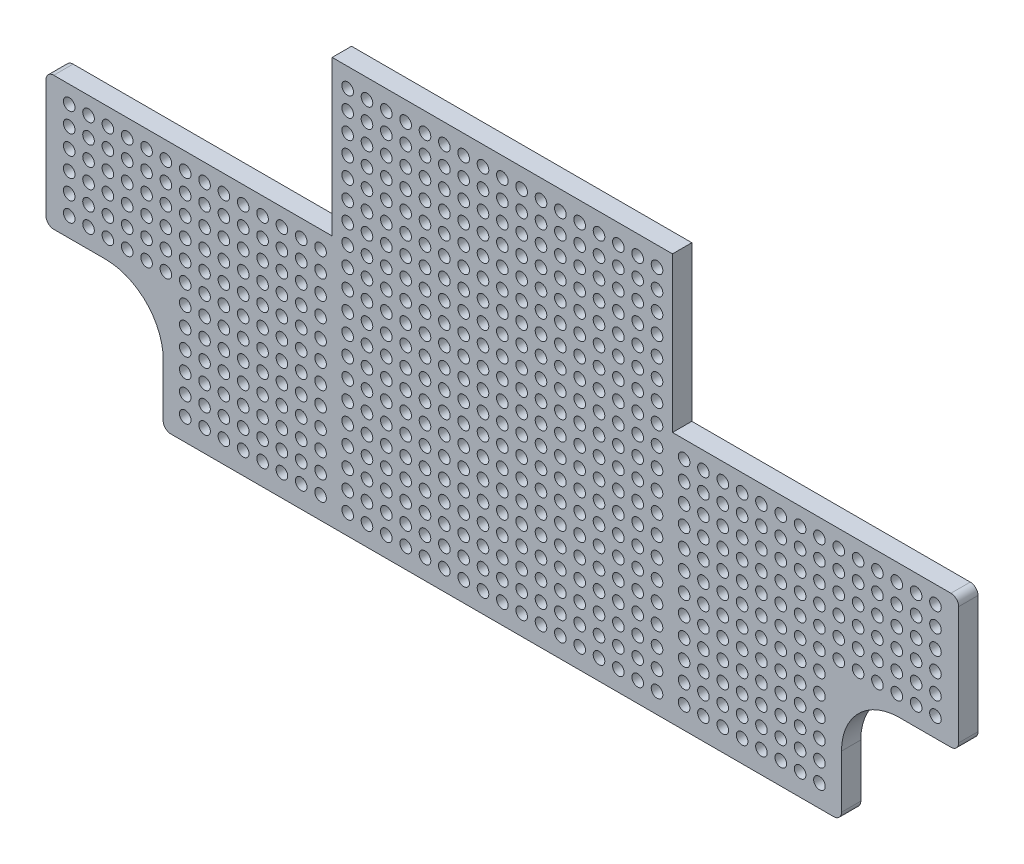
SolidWorks part; units mm, degrees
ref_plane "Plan de face" through (0, 0, 0) normal (0, 0, 1) x (1, 0, 0)
ref_plane "Plan de dessus" through (0, 0, 0) normal (0, 1, 0) x (1, 0, 0)
ref_plane "Plan de droite" through (0, 0, 0) normal (1, 0, 0) x (0, 0, -1)
sketch "Esquisse1" plane through (0, 0, 0) normal (0, 0, 1) x (1, 0, 0)
  line L0 (0, 0) -> (236, 0)
  line L1 (236, 0) -> (236, 65.2)
  line L2 (236, 65.2) -> (162, 65.2)
  line L3 (162, 65.2) -> (162, 105.2)
  line L4 (162, 105.2) -> (74, 105.2)
  line L5 (74, 105.2) -> (74, 65.2)
  line L6 (74, 65.2) -> (0, 65.2)
  line L7 (0, 65.2) -> (0, 0)
  line L8 (0, 30.7) -> (33, 30.7)
  line L10 (236, 30.7) -> (203, 30.7)
  line L12 (30.3, 30.7) -> (30.3, 0)
  line L13 (205.7, 30.7) -> (205.7, 0)
  circle A0 centre (15.3, 15.7) radius 15
  circle A1 centre (220.7, 15.7) radius 15
  circle A2 centre (78, 85.2) radius 1.5
  circle A3 centre (98, 85.2) radius 1.5
  circle A4 centre (118, 85.2) radius 1.5
  circle A5 centre (138, 85.2) radius 1.5
  circle A6 centre (158, 85.2) radius 1.5
  circle A7 centre (6, 55.7) radius 1.5
  circle A8 centre (26, 55.7) radius 1.5
  circle A9 centre (26, 35.7) radius 1.5
  circle A10 centre (6, 35.7) radius 1.5
  circle A11 centre (210, 55.7) radius 1.5
  circle A12 centre (230, 55.7) radius 1.5
  circle A13 centre (210, 35.7) radius 1.5
  circle A14 centre (230, 35.7) radius 1.5
  circle A15 centre (83, 85.2) radius 1.5
  circle A16 centre (88, 85.2) radius 1.5
  circle A17 centre (93, 85.2) radius 1.5
  circle A18 centre (98, 85.2) radius 1.5
  circle A19 centre (103, 85.2) radius 1.5
  circle A20 centre (108, 85.2) radius 1.5
  circle A21 centre (113, 85.2) radius 1.5
  circle A22 centre (118, 85.2) radius 1.5
  circle A23 centre (123, 85.2) radius 1.5
  circle A24 centre (128, 85.2) radius 1.5
  circle A25 centre (133, 85.2) radius 1.5
  circle A26 centre (138, 85.2) radius 1.5
  circle A27 centre (143, 85.2) radius 1.5
  circle A28 centre (148, 85.2) radius 1.5
  circle A29 centre (153, 85.2) radius 1.5
  circle A30 centre (158, 85.2) radius 1.5
  circle A31 centre (83, 90.2) radius 1.5
  circle A32 centre (88, 90.2) radius 1.5
  circle A33 centre (93, 90.2) radius 1.5
  circle A34 centre (98, 90.2) radius 1.5
  circle A35 centre (103, 90.2) radius 1.5
  circle A36 centre (108, 90.2) radius 1.5
  circle A37 centre (113, 90.2) radius 1.5
  circle A38 centre (118, 90.2) radius 1.5
  circle A39 centre (123, 90.2) radius 1.5
  circle A40 centre (128, 90.2) radius 1.5
  circle A41 centre (133, 90.2) radius 1.5
  circle A42 centre (138, 90.2) radius 1.5
  circle A43 centre (143, 90.2) radius 1.5
  circle A44 centre (148, 90.2) radius 1.5
  circle A45 centre (153, 90.2) radius 1.5
  circle A46 centre (158, 90.2) radius 1.5
  circle A47 centre (83, 95.2) radius 1.5
  circle A48 centre (88, 95.2) radius 1.5
  circle A49 centre (93, 95.2) radius 1.5
  circle A50 centre (98, 95.2) radius 1.5
  circle A51 centre (103, 95.2) radius 1.5
  circle A52 centre (108, 95.2) radius 1.5
  circle A53 centre (113, 95.2) radius 1.5
  circle A54 centre (118, 95.2) radius 1.5
  circle A55 centre (123, 95.2) radius 1.5
  circle A56 centre (128, 95.2) radius 1.5
  circle A57 centre (133, 95.2) radius 1.5
  circle A58 centre (138, 95.2) radius 1.5
  circle A59 centre (143, 95.2) radius 1.5
  circle A60 centre (148, 95.2) radius 1.5
  circle A61 centre (153, 95.2) radius 1.5
  circle A62 centre (158, 95.2) radius 1.5
  circle A63 centre (83, 100.2) radius 1.5
  circle A64 centre (88, 100.2) radius 1.5
  circle A65 centre (93, 100.2) radius 1.5
  circle A66 centre (98, 100.2) radius 1.5
  circle A67 centre (103, 100.2) radius 1.5
  circle A68 centre (108, 100.2) radius 1.5
  circle A69 centre (113, 100.2) radius 1.5
  circle A70 centre (118, 100.2) radius 1.5
  circle A71 centre (123, 100.2) radius 1.5
  circle A72 centre (128, 100.2) radius 1.5
  circle A73 centre (133, 100.2) radius 1.5
  circle A74 centre (138, 100.2) radius 1.5
  circle A75 centre (143, 100.2) radius 1.5
  circle A76 centre (148, 100.2) radius 1.5
  circle A77 centre (153, 100.2) radius 1.5
  circle A78 centre (158, 100.2) radius 1.5
  circle A79 centre (78, 90.2) radius 1.5
  circle A80 centre (78, 95.2) radius 1.5
  circle A81 centre (78, 100.2) radius 1.5
  circle A82 centre (83, 85.2) radius 1.5
  circle A83 centre (88, 85.2) radius 1.5
  circle A84 centre (93, 85.2) radius 1.5
  circle A85 centre (98, 85.2) radius 1.5
  circle A86 centre (103, 85.2) radius 1.5
  circle A87 centre (108, 85.2) radius 1.5
  circle A88 centre (113, 85.2) radius 1.5
  circle A89 centre (118, 85.2) radius 1.5
  circle A90 centre (123, 85.2) radius 1.5
  circle A91 centre (128, 85.2) radius 1.5
  circle A92 centre (133, 85.2) radius 1.5
  circle A93 centre (138, 85.2) radius 1.5
  circle A94 centre (143, 85.2) radius 1.5
  circle A95 centre (148, 85.2) radius 1.5
  circle A96 centre (153, 85.2) radius 1.5
  circle A97 centre (158, 85.2) radius 1.5
  circle A98 centre (83, 80.2) radius 1.5
  circle A99 centre (88, 80.2) radius 1.5
  circle A100 centre (93, 80.2) radius 1.5
  circle A101 centre (98, 80.2) radius 1.5
  circle A102 centre (103, 80.2) radius 1.5
  circle A103 centre (108, 80.2) radius 1.5
  circle A104 centre (113, 80.2) radius 1.5
  circle A105 centre (118, 80.2) radius 1.5
  circle A106 centre (123, 80.2) radius 1.5
  circle A107 centre (128, 80.2) radius 1.5
  circle A108 centre (133, 80.2) radius 1.5
  circle A109 centre (138, 80.2) radius 1.5
  circle A110 centre (143, 80.2) radius 1.5
  circle A111 centre (148, 80.2) radius 1.5
  circle A112 centre (153, 80.2) radius 1.5
  circle A113 centre (158, 80.2) radius 1.5
  circle A114 centre (83, 75.2) radius 1.5
  circle A115 centre (88, 75.2) radius 1.5
  circle A116 centre (93, 75.2) radius 1.5
  circle A117 centre (98, 75.2) radius 1.5
  circle A118 centre (103, 75.2) radius 1.5
  circle A119 centre (108, 75.2) radius 1.5
  circle A120 centre (113, 75.2) radius 1.5
  circle A121 centre (118, 75.2) radius 1.5
  circle A122 centre (123, 75.2) radius 1.5
  circle A123 centre (128, 75.2) radius 1.5
  circle A124 centre (133, 75.2) radius 1.5
  circle A125 centre (138, 75.2) radius 1.5
  circle A126 centre (143, 75.2) radius 1.5
  circle A127 centre (148, 75.2) radius 1.5
  circle A128 centre (153, 75.2) radius 1.5
  circle A129 centre (158, 75.2) radius 1.5
  circle A130 centre (83, 70.2) radius 1.5
  circle A131 centre (88, 70.2) radius 1.5
  circle A132 centre (93, 70.2) radius 1.5
  circle A133 centre (98, 70.2) radius 1.5
  circle A134 centre (103, 70.2) radius 1.5
  circle A135 centre (108, 70.2) radius 1.5
  circle A136 centre (113, 70.2) radius 1.5
  circle A137 centre (118, 70.2) radius 1.5
  circle A138 centre (123, 70.2) radius 1.5
  circle A139 centre (128, 70.2) radius 1.5
  circle A140 centre (133, 70.2) radius 1.5
  circle A141 centre (138, 70.2) radius 1.5
  circle A142 centre (143, 70.2) radius 1.5
  circle A143 centre (148, 70.2) radius 1.5
  circle A144 centre (153, 70.2) radius 1.5
  circle A145 centre (158, 70.2) radius 1.5
  circle A146 centre (83, 65.2) radius 1.5
  circle A147 centre (88, 65.2) radius 1.5
  circle A148 centre (93, 65.2) radius 1.5
  circle A149 centre (98, 65.2) radius 1.5
  circle A150 centre (103, 65.2) radius 1.5
  circle A151 centre (108, 65.2) radius 1.5
  circle A152 centre (113, 65.2) radius 1.5
  circle A153 centre (118, 65.2) radius 1.5
  circle A154 centre (123, 65.2) radius 1.5
  circle A155 centre (128, 65.2) radius 1.5
  circle A156 centre (133, 65.2) radius 1.5
  circle A157 centre (138, 65.2) radius 1.5
  circle A158 centre (143, 65.2) radius 1.5
  circle A159 centre (148, 65.2) radius 1.5
  circle A160 centre (153, 65.2) radius 1.5
  circle A161 centre (158, 65.2) radius 1.5
  circle A162 centre (78, 80.2) radius 1.5
  circle A163 centre (78, 75.2) radius 1.5
  circle A164 centre (78, 70.2) radius 1.5
  circle A165 centre (78, 65.2) radius 1.5
  circle A166 centre (11, 55.7) radius 1.5
  circle A167 centre (16, 55.7) radius 1.5
  circle A168 centre (21, 55.7) radius 1.5
  circle A169 centre (26, 55.7) radius 1.5
  circle A170 centre (31, 55.7) radius 1.5
  circle A171 centre (36, 55.7) radius 1.5
  circle A172 centre (41, 55.7) radius 1.5
  circle A173 centre (46, 55.7) radius 1.5
  circle A174 centre (51, 55.7) radius 1.5
  circle A175 centre (56, 55.7) radius 1.5
  circle A176 centre (61, 55.7) radius 1.5
  circle A177 centre (66, 55.7) radius 1.5
  circle A178 centre (71, 55.7) radius 1.5
  circle A179 centre (11, 60.7) radius 1.5
  circle A180 centre (16, 60.7) radius 1.5
  circle A181 centre (21, 60.7) radius 1.5
  circle A182 centre (26, 60.7) radius 1.5
  circle A183 centre (31, 60.7) radius 1.5
  circle A184 centre (36, 60.7) radius 1.5
  circle A185 centre (41, 60.7) radius 1.5
  circle A186 centre (46, 60.7) radius 1.5
  circle A187 centre (51, 60.7) radius 1.5
  circle A188 centre (56, 60.7) radius 1.5
  circle A189 centre (61, 60.7) radius 1.5
  circle A190 centre (66, 60.7) radius 1.5
  circle A191 centre (71, 60.7) radius 1.5
  circle A192 centre (6, 60.7) radius 1.5
  circle A193 centre (11, 55.7) radius 1.5
  circle A194 centre (16, 55.7) radius 1.5
  circle A195 centre (21, 55.7) radius 1.5
  circle A196 centre (26, 55.7) radius 1.5
  circle A197 centre (31, 55.7) radius 1.5
  circle A198 centre (36, 55.7) radius 1.5
  circle A199 centre (41, 55.7) radius 1.5
  circle A200 centre (46, 55.7) radius 1.5
  circle A201 centre (51, 55.7) radius 1.5
  circle A202 centre (56, 55.7) radius 1.5
  circle A203 centre (61, 55.7) radius 1.5
  circle A204 centre (66, 55.7) radius 1.5
  circle A205 centre (71, 55.7) radius 1.5
  circle A206 centre (11, 50.7) radius 1.5
  circle A207 centre (16, 50.7) radius 1.5
  circle A208 centre (21, 50.7) radius 1.5
  circle A209 centre (26, 50.7) radius 1.5
  circle A210 centre (31, 50.7) radius 1.5
  circle A211 centre (36, 50.7) radius 1.5
  circle A212 centre (41, 50.7) radius 1.5
  circle A213 centre (46, 50.7) radius 1.5
  circle A214 centre (51, 50.7) radius 1.5
  circle A215 centre (56, 50.7) radius 1.5
  circle A216 centre (61, 50.7) radius 1.5
  circle A217 centre (66, 50.7) radius 1.5
  circle A218 centre (71, 50.7) radius 1.5
  circle A219 centre (11, 45.7) radius 1.5
  circle A220 centre (16, 45.7) radius 1.5
  circle A221 centre (21, 45.7) radius 1.5
  circle A222 centre (26, 45.7) radius 1.5
  circle A223 centre (31, 45.7) radius 1.5
  circle A224 centre (36, 45.7) radius 1.5
  circle A225 centre (41, 45.7) radius 1.5
  circle A226 centre (46, 45.7) radius 1.5
  circle A227 centre (51, 45.7) radius 1.5
  circle A228 centre (56, 45.7) radius 1.5
  circle A229 centre (61, 45.7) radius 1.5
  circle A230 centre (66, 45.7) radius 1.5
  circle A231 centre (71, 45.7) radius 1.5
  circle A232 centre (11, 40.7) radius 1.5
  circle A233 centre (16, 40.7) radius 1.5
  circle A234 centre (21, 40.7) radius 1.5
  circle A235 centre (26, 40.7) radius 1.5
  circle A236 centre (31, 40.7) radius 1.5
  circle A237 centre (36, 40.7) radius 1.5
  circle A238 centre (41, 40.7) radius 1.5
  circle A239 centre (46, 40.7) radius 1.5
  circle A240 centre (51, 40.7) radius 1.5
  circle A241 centre (56, 40.7) radius 1.5
  circle A242 centre (61, 40.7) radius 1.5
  circle A243 centre (66, 40.7) radius 1.5
  circle A244 centre (71, 40.7) radius 1.5
  circle A245 centre (11, 35.7) radius 1.5
  circle A246 centre (16, 35.7) radius 1.5
  circle A247 centre (21, 35.7) radius 1.5
  circle A248 centre (26, 35.7) radius 1.5
  circle A249 centre (31, 35.7) radius 1.5
  circle A250 centre (36, 35.7) radius 1.5
  circle A251 centre (41, 35.7) radius 1.5
  circle A252 centre (46, 35.7) radius 1.5
  circle A253 centre (51, 35.7) radius 1.5
  circle A254 centre (56, 35.7) radius 1.5
  circle A255 centre (61, 35.7) radius 1.5
  circle A256 centre (66, 35.7) radius 1.5
  circle A257 centre (71, 35.7) radius 1.5
  circle A258 centre (6, 50.7) radius 1.5
  circle A259 centre (6, 45.7) radius 1.5
  circle A260 centre (6, 40.7) radius 1.5
  circle A261 centre (6, 35.7) radius 1.5
  circle A262 centre (41, 35.7) radius 1.5
  circle A263 centre (46, 35.7) radius 1.5
  circle A264 centre (51, 35.7) radius 1.5
  circle A265 centre (56, 35.7) radius 1.5
  circle A266 centre (61, 35.7) radius 1.5
  circle A267 centre (66, 35.7) radius 1.5
  circle A268 centre (71, 35.7) radius 1.5
  circle A269 centre (41, 30.7) radius 1.5
  circle A270 centre (46, 30.7) radius 1.5
  circle A271 centre (51, 30.7) radius 1.5
  circle A272 centre (56, 30.7) radius 1.5
  circle A273 centre (61, 30.7) radius 1.5
  circle A274 centre (66, 30.7) radius 1.5
  circle A275 centre (71, 30.7) radius 1.5
  circle A276 centre (41, 25.7) radius 1.5
  circle A277 centre (46, 25.7) radius 1.5
  circle A278 centre (51, 25.7) radius 1.5
  circle A279 centre (56, 25.7) radius 1.5
  circle A280 centre (61, 25.7) radius 1.5
  circle A281 centre (66, 25.7) radius 1.5
  circle A282 centre (71, 25.7) radius 1.5
  circle A283 centre (41, 20.7) radius 1.5
  circle A284 centre (46, 20.7) radius 1.5
  circle A285 centre (51, 20.7) radius 1.5
  circle A286 centre (56, 20.7) radius 1.5
  circle A287 centre (61, 20.7) radius 1.5
  circle A288 centre (66, 20.7) radius 1.5
  circle A289 centre (71, 20.7) radius 1.5
  circle A290 centre (41, 15.7) radius 1.5
  circle A291 centre (46, 15.7) radius 1.5
  circle A292 centre (51, 15.7) radius 1.5
  circle A293 centre (56, 15.7) radius 1.5
  circle A294 centre (61, 15.7) radius 1.5
  circle A295 centre (66, 15.7) radius 1.5
  circle A296 centre (71, 15.7) radius 1.5
  circle A297 centre (41, 10.7) radius 1.5
  circle A298 centre (46, 10.7) radius 1.5
  circle A299 centre (51, 10.7) radius 1.5
  circle A300 centre (56, 10.7) radius 1.5
  circle A301 centre (61, 10.7) radius 1.5
  circle A302 centre (66, 10.7) radius 1.5
  circle A303 centre (71, 10.7) radius 1.5
  circle A304 centre (41, 5.7) radius 1.5
  circle A305 centre (46, 5.7) radius 1.5
  circle A306 centre (51, 5.7) radius 1.5
  circle A307 centre (56, 5.7) radius 1.5
  circle A308 centre (61, 5.7) radius 1.5
  circle A309 centre (66, 5.7) radius 1.5
  circle A310 centre (71, 5.7) radius 1.5
  circle A311 centre (36, 30.7) radius 1.5
  circle A312 centre (36, 25.7) radius 1.5
  circle A313 centre (36, 20.7) radius 1.5
  circle A314 centre (36, 15.7) radius 1.5
  circle A315 centre (36, 10.7) radius 1.5
  circle A316 centre (36, 5.7) radius 1.5
  circle A317 centre (83, 65.2) radius 1.5
  circle A318 centre (88, 65.2) radius 1.5
  circle A319 centre (93, 65.2) radius 1.5
  circle A320 centre (98, 65.2) radius 1.5
  circle A321 centre (103, 65.2) radius 1.5
  circle A322 centre (108, 65.2) radius 1.5
  circle A323 centre (113, 65.2) radius 1.5
  circle A324 centre (118, 65.2) radius 1.5
  circle A325 centre (123, 65.2) radius 1.5
  circle A326 centre (128, 65.2) radius 1.5
  circle A327 centre (133, 65.2) radius 1.5
  circle A328 centre (138, 65.2) radius 1.5
  circle A329 centre (143, 65.2) radius 1.5
  circle A330 centre (148, 65.2) radius 1.5
  circle A331 centre (153, 65.2) radius 1.5
  circle A332 centre (158, 65.2) radius 1.5
  circle A333 centre (83, 60.2) radius 1.5
  circle A334 centre (88, 60.2) radius 1.5
  circle A335 centre (93, 60.2) radius 1.5
  circle A336 centre (98, 60.2) radius 1.5
  circle A337 centre (103, 60.2) radius 1.5
  circle A338 centre (108, 60.2) radius 1.5
  circle A339 centre (113, 60.2) radius 1.5
  circle A340 centre (118, 60.2) radius 1.5
  circle A341 centre (123, 60.2) radius 1.5
  circle A342 centre (128, 60.2) radius 1.5
  circle A343 centre (133, 60.2) radius 1.5
  circle A344 centre (138, 60.2) radius 1.5
  circle A345 centre (143, 60.2) radius 1.5
  circle A346 centre (148, 60.2) radius 1.5
  circle A347 centre (153, 60.2) radius 1.5
  circle A348 centre (158, 60.2) radius 1.5
  circle A349 centre (83, 55.2) radius 1.5
  circle A350 centre (88, 55.2) radius 1.5
  circle A351 centre (93, 55.2) radius 1.5
  circle A352 centre (98, 55.2) radius 1.5
  circle A353 centre (103, 55.2) radius 1.5
  circle A354 centre (108, 55.2) radius 1.5
  circle A355 centre (113, 55.2) radius 1.5
  circle A356 centre (118, 55.2) radius 1.5
  circle A357 centre (123, 55.2) radius 1.5
  circle A358 centre (128, 55.2) radius 1.5
  circle A359 centre (133, 55.2) radius 1.5
  circle A360 centre (138, 55.2) radius 1.5
  circle A361 centre (143, 55.2) radius 1.5
  circle A362 centre (148, 55.2) radius 1.5
  circle A363 centre (153, 55.2) radius 1.5
  circle A364 centre (158, 55.2) radius 1.5
  circle A365 centre (83, 50.2) radius 1.5
  circle A366 centre (88, 50.2) radius 1.5
  circle A367 centre (93, 50.2) radius 1.5
  circle A368 centre (98, 50.2) radius 1.5
  circle A369 centre (103, 50.2) radius 1.5
  circle A370 centre (108, 50.2) radius 1.5
  circle A371 centre (113, 50.2) radius 1.5
  circle A372 centre (118, 50.2) radius 1.5
  circle A373 centre (123, 50.2) radius 1.5
  circle A374 centre (128, 50.2) radius 1.5
  circle A375 centre (133, 50.2) radius 1.5
  circle A376 centre (138, 50.2) radius 1.5
  circle A377 centre (143, 50.2) radius 1.5
  circle A378 centre (148, 50.2) radius 1.5
  circle A379 centre (153, 50.2) radius 1.5
  circle A380 centre (158, 50.2) radius 1.5
  circle A381 centre (83, 45.2) radius 1.5
  circle A382 centre (88, 45.2) radius 1.5
  circle A383 centre (93, 45.2) radius 1.5
  circle A384 centre (98, 45.2) radius 1.5
  circle A385 centre (103, 45.2) radius 1.5
  circle A386 centre (108, 45.2) radius 1.5
  circle A387 centre (113, 45.2) radius 1.5
  circle A388 centre (118, 45.2) radius 1.5
  circle A389 centre (123, 45.2) radius 1.5
  circle A390 centre (128, 45.2) radius 1.5
  circle A391 centre (133, 45.2) radius 1.5
  circle A392 centre (138, 45.2) radius 1.5
  circle A393 centre (143, 45.2) radius 1.5
  circle A394 centre (148, 45.2) radius 1.5
  circle A395 centre (153, 45.2) radius 1.5
  circle A396 centre (158, 45.2) radius 1.5
  circle A397 centre (83, 40.2) radius 1.5
  circle A398 centre (88, 40.2) radius 1.5
  circle A399 centre (93, 40.2) radius 1.5
  circle A400 centre (98, 40.2) radius 1.5
  circle A401 centre (103, 40.2) radius 1.5
  circle A402 centre (108, 40.2) radius 1.5
  circle A403 centre (113, 40.2) radius 1.5
  circle A404 centre (118, 40.2) radius 1.5
  circle A405 centre (123, 40.2) radius 1.5
  circle A406 centre (128, 40.2) radius 1.5
  circle A407 centre (133, 40.2) radius 1.5
  circle A408 centre (138, 40.2) radius 1.5
  circle A409 centre (143, 40.2) radius 1.5
  circle A410 centre (148, 40.2) radius 1.5
  circle A411 centre (153, 40.2) radius 1.5
  circle A412 centre (158, 40.2) radius 1.5
  circle A413 centre (83, 35.2) radius 1.5
  circle A414 centre (88, 35.2) radius 1.5
  circle A415 centre (93, 35.2) radius 1.5
  circle A416 centre (98, 35.2) radius 1.5
  circle A417 centre (103, 35.2) radius 1.5
  circle A418 centre (108, 35.2) radius 1.5
  circle A419 centre (113, 35.2) radius 1.5
  circle A420 centre (118, 35.2) radius 1.5
  circle A421 centre (123, 35.2) radius 1.5
  circle A422 centre (128, 35.2) radius 1.5
  circle A423 centre (133, 35.2) radius 1.5
  circle A424 centre (138, 35.2) radius 1.5
  circle A425 centre (143, 35.2) radius 1.5
  circle A426 centre (148, 35.2) radius 1.5
  circle A427 centre (153, 35.2) radius 1.5
  circle A428 centre (158, 35.2) radius 1.5
  circle A429 centre (83, 30.2) radius 1.5
  circle A430 centre (88, 30.2) radius 1.5
  circle A431 centre (93, 30.2) radius 1.5
  circle A432 centre (98, 30.2) radius 1.5
  circle A433 centre (103, 30.2) radius 1.5
  circle A434 centre (108, 30.2) radius 1.5
  circle A435 centre (113, 30.2) radius 1.5
  circle A436 centre (118, 30.2) radius 1.5
  circle A437 centre (123, 30.2) radius 1.5
  circle A438 centre (128, 30.2) radius 1.5
  circle A439 centre (133, 30.2) radius 1.5
  circle A440 centre (138, 30.2) radius 1.5
  circle A441 centre (143, 30.2) radius 1.5
  circle A442 centre (148, 30.2) radius 1.5
  circle A443 centre (153, 30.2) radius 1.5
  circle A444 centre (158, 30.2) radius 1.5
  circle A445 centre (83, 25.2) radius 1.5
  circle A446 centre (88, 25.2) radius 1.5
  circle A447 centre (93, 25.2) radius 1.5
  circle A448 centre (98, 25.2) radius 1.5
  circle A449 centre (103, 25.2) radius 1.5
  circle A450 centre (108, 25.2) radius 1.5
  circle A451 centre (113, 25.2) radius 1.5
  circle A452 centre (118, 25.2) radius 1.5
  circle A453 centre (123, 25.2) radius 1.5
  circle A454 centre (128, 25.2) radius 1.5
  circle A455 centre (133, 25.2) radius 1.5
  circle A456 centre (138, 25.2) radius 1.5
  circle A457 centre (143, 25.2) radius 1.5
  circle A458 centre (148, 25.2) radius 1.5
  circle A459 centre (153, 25.2) radius 1.5
  circle A460 centre (158, 25.2) radius 1.5
  circle A461 centre (83, 20.2) radius 1.5
  circle A462 centre (88, 20.2) radius 1.5
  circle A463 centre (93, 20.2) radius 1.5
  circle A464 centre (98, 20.2) radius 1.5
  circle A465 centre (103, 20.2) radius 1.5
  circle A466 centre (108, 20.2) radius 1.5
  circle A467 centre (113, 20.2) radius 1.5
  circle A468 centre (118, 20.2) radius 1.5
  circle A469 centre (123, 20.2) radius 1.5
  circle A470 centre (128, 20.2) radius 1.5
  circle A471 centre (133, 20.2) radius 1.5
  circle A472 centre (138, 20.2) radius 1.5
  circle A473 centre (143, 20.2) radius 1.5
  circle A474 centre (148, 20.2) radius 1.5
  circle A475 centre (153, 20.2) radius 1.5
  circle A476 centre (158, 20.2) radius 1.5
  circle A477 centre (83, 15.2) radius 1.5
  circle A478 centre (88, 15.2) radius 1.5
  circle A479 centre (93, 15.2) radius 1.5
  circle A480 centre (98, 15.2) radius 1.5
  circle A481 centre (103, 15.2) radius 1.5
  circle A482 centre (108, 15.2) radius 1.5
  circle A483 centre (113, 15.2) radius 1.5
  circle A484 centre (118, 15.2) radius 1.5
  circle A485 centre (123, 15.2) radius 1.5
  circle A486 centre (128, 15.2) radius 1.5
  circle A487 centre (133, 15.2) radius 1.5
  circle A488 centre (138, 15.2) radius 1.5
  circle A489 centre (143, 15.2) radius 1.5
  circle A490 centre (148, 15.2) radius 1.5
  circle A491 centre (153, 15.2) radius 1.5
  circle A492 centre (158, 15.2) radius 1.5
  circle A493 centre (83, 10.2) radius 1.5
  circle A494 centre (88, 10.2) radius 1.5
  circle A495 centre (93, 10.2) radius 1.5
  circle A496 centre (98, 10.2) radius 1.5
  circle A497 centre (103, 10.2) radius 1.5
  circle A498 centre (108, 10.2) radius 1.5
  circle A499 centre (113, 10.2) radius 1.5
  circle A500 centre (118, 10.2) radius 1.5
  circle A501 centre (123, 10.2) radius 1.5
  circle A502 centre (128, 10.2) radius 1.5
  circle A503 centre (133, 10.2) radius 1.5
  circle A504 centre (138, 10.2) radius 1.5
  circle A505 centre (143, 10.2) radius 1.5
  circle A506 centre (148, 10.2) radius 1.5
  circle A507 centre (153, 10.2) radius 1.5
  circle A508 centre (158, 10.2) radius 1.5
  circle A509 centre (83, 5.2) radius 1.5
  circle A510 centre (88, 5.2) radius 1.5
  circle A511 centre (93, 5.2) radius 1.5
  circle A512 centre (98, 5.2) radius 1.5
  circle A513 centre (103, 5.2) radius 1.5
  circle A514 centre (108, 5.2) radius 1.5
  circle A515 centre (113, 5.2) radius 1.5
  circle A516 centre (118, 5.2) radius 1.5
  circle A517 centre (123, 5.2) radius 1.5
  circle A518 centre (128, 5.2) radius 1.5
  circle A519 centre (133, 5.2) radius 1.5
  circle A520 centre (138, 5.2) radius 1.5
  circle A521 centre (143, 5.2) radius 1.5
  circle A522 centre (148, 5.2) radius 1.5
  circle A523 centre (153, 5.2) radius 1.5
  circle A524 centre (158, 5.2) radius 1.5
  circle A525 centre (78, 60.2) radius 1.5
  circle A526 centre (78, 55.2) radius 1.5
  circle A527 centre (78, 50.2) radius 1.5
  circle A528 centre (78, 45.2) radius 1.5
  circle A529 centre (78, 40.2) radius 1.5
  circle A530 centre (78, 35.2) radius 1.5
  circle A531 centre (78, 30.2) radius 1.5
  circle A532 centre (78, 25.2) radius 1.5
  circle A533 centre (78, 20.2) radius 1.5
  circle A534 centre (78, 15.2) radius 1.5
  circle A535 centre (78, 10.2) radius 1.5
  circle A536 centre (78, 5.2) radius 1.5
  circle A537 centre (225, 55.7) radius 1.5
  circle A538 centre (220, 55.7) radius 1.5
  circle A539 centre (215, 55.7) radius 1.5
  circle A540 centre (210, 55.7) radius 1.5
  circle A541 centre (205, 55.7) radius 1.5
  circle A542 centre (200, 55.7) radius 1.5
  circle A543 centre (195, 55.7) radius 1.5
  circle A544 centre (190, 55.7) radius 1.5
  circle A545 centre (185, 55.7) radius 1.5
  circle A546 centre (180, 55.7) radius 1.5
  circle A547 centre (175, 55.7) radius 1.5
  circle A548 centre (170, 55.7) radius 1.5
  circle A549 centre (165, 55.7) radius 1.5
  circle A550 centre (225, 60.7) radius 1.5
  circle A551 centre (220, 60.7) radius 1.5
  circle A552 centre (215, 60.7) radius 1.5
  circle A553 centre (210, 60.7) radius 1.5
  circle A554 centre (205, 60.7) radius 1.5
  circle A555 centre (200, 60.7) radius 1.5
  circle A556 centre (195, 60.7) radius 1.5
  circle A557 centre (190, 60.7) radius 1.5
  circle A558 centre (185, 60.7) radius 1.5
  circle A559 centre (180, 60.7) radius 1.5
  circle A560 centre (175, 60.7) radius 1.5
  circle A561 centre (170, 60.7) radius 1.5
  circle A562 centre (165, 60.7) radius 1.5
  circle A563 centre (230, 60.7) radius 1.5
  circle A564 centre (225, 55.7) radius 1.5
  circle A565 centre (220, 55.7) radius 1.5
  circle A566 centre (215, 55.7) radius 1.5
  circle A567 centre (210, 55.7) radius 1.5
  circle A568 centre (205, 55.7) radius 1.5
  circle A569 centre (200, 55.7) radius 1.5
  circle A570 centre (195, 55.7) radius 1.5
  circle A571 centre (190, 55.7) radius 1.5
  circle A572 centre (185, 55.7) radius 1.5
  circle A573 centre (180, 55.7) radius 1.5
  circle A574 centre (175, 55.7) radius 1.5
  circle A575 centre (170, 55.7) radius 1.5
  circle A576 centre (165, 55.7) radius 1.5
  circle A577 centre (225, 50.7) radius 1.5
  circle A578 centre (220, 50.7) radius 1.5
  circle A579 centre (215, 50.7) radius 1.5
  circle A580 centre (210, 50.7) radius 1.5
  circle A581 centre (205, 50.7) radius 1.5
  circle A582 centre (200, 50.7) radius 1.5
  circle A583 centre (195, 50.7) radius 1.5
  circle A584 centre (190, 50.7) radius 1.5
  circle A585 centre (185, 50.7) radius 1.5
  circle A586 centre (180, 50.7) radius 1.5
  circle A587 centre (175, 50.7) radius 1.5
  circle A588 centre (170, 50.7) radius 1.5
  circle A589 centre (165, 50.7) radius 1.5
  circle A590 centre (225, 45.7) radius 1.5
  circle A591 centre (220, 45.7) radius 1.5
  circle A592 centre (215, 45.7) radius 1.5
  circle A593 centre (210, 45.7) radius 1.5
  circle A594 centre (205, 45.7) radius 1.5
  circle A595 centre (200, 45.7) radius 1.5
  circle A596 centre (195, 45.7) radius 1.5
  circle A597 centre (190, 45.7) radius 1.5
  circle A598 centre (185, 45.7) radius 1.5
  circle A599 centre (180, 45.7) radius 1.5
  circle A600 centre (175, 45.7) radius 1.5
  circle A601 centre (170, 45.7) radius 1.5
  circle A602 centre (165, 45.7) radius 1.5
  circle A603 centre (225, 40.7) radius 1.5
  circle A604 centre (220, 40.7) radius 1.5
  circle A605 centre (215, 40.7) radius 1.5
  circle A606 centre (210, 40.7) radius 1.5
  circle A607 centre (205, 40.7) radius 1.5
  circle A608 centre (200, 40.7) radius 1.5
  circle A609 centre (195, 40.7) radius 1.5
  circle A610 centre (190, 40.7) radius 1.5
  circle A611 centre (185, 40.7) radius 1.5
  circle A612 centre (180, 40.7) radius 1.5
  circle A613 centre (175, 40.7) radius 1.5
  circle A614 centre (170, 40.7) radius 1.5
  circle A615 centre (165, 40.7) radius 1.5
  circle A616 centre (225, 35.7) radius 1.5
  circle A617 centre (220, 35.7) radius 1.5
  circle A618 centre (215, 35.7) radius 1.5
  circle A619 centre (210, 35.7) radius 1.5
  circle A620 centre (205, 35.7) radius 1.5
  circle A621 centre (200, 35.7) radius 1.5
  circle A622 centre (195, 35.7) radius 1.5
  circle A623 centre (190, 35.7) radius 1.5
  circle A624 centre (185, 35.7) radius 1.5
  circle A625 centre (180, 35.7) radius 1.5
  circle A626 centre (175, 35.7) radius 1.5
  circle A627 centre (170, 35.7) radius 1.5
  circle A628 centre (165, 35.7) radius 1.5
  circle A629 centre (230, 50.7) radius 1.5
  circle A630 centre (230, 45.7) radius 1.5
  circle A631 centre (230, 40.7) radius 1.5
  circle A632 centre (230, 35.7) radius 1.5
  circle A633 centre (195, 35.7) radius 1.5
  circle A634 centre (190, 35.7) radius 1.5
  circle A635 centre (185, 35.7) radius 1.5
  circle A636 centre (180, 35.7) radius 1.5
  circle A637 centre (175, 35.7) radius 1.5
  circle A638 centre (170, 35.7) radius 1.5
  circle A639 centre (165, 35.7) radius 1.5
  circle A640 centre (195, 30.7) radius 1.5
  circle A641 centre (190, 30.7) radius 1.5
  circle A642 centre (185, 30.7) radius 1.5
  circle A643 centre (180, 30.7) radius 1.5
  circle A644 centre (175, 30.7) radius 1.5
  circle A645 centre (170, 30.7) radius 1.5
  circle A646 centre (165, 30.7) radius 1.5
  circle A647 centre (195, 25.7) radius 1.5
  circle A648 centre (190, 25.7) radius 1.5
  circle A649 centre (185, 25.7) radius 1.5
  circle A650 centre (180, 25.7) radius 1.5
  circle A651 centre (175, 25.7) radius 1.5
  circle A652 centre (170, 25.7) radius 1.5
  circle A653 centre (165, 25.7) radius 1.5
  circle A654 centre (195, 20.7) radius 1.5
  circle A655 centre (190, 20.7) radius 1.5
  circle A656 centre (185, 20.7) radius 1.5
  circle A657 centre (180, 20.7) radius 1.5
  circle A658 centre (175, 20.7) radius 1.5
  circle A659 centre (170, 20.7) radius 1.5
  circle A660 centre (165, 20.7) radius 1.5
  circle A661 centre (195, 15.7) radius 1.5
  circle A662 centre (190, 15.7) radius 1.5
  circle A663 centre (185, 15.7) radius 1.5
  circle A664 centre (180, 15.7) radius 1.5
  circle A665 centre (175, 15.7) radius 1.5
  circle A666 centre (170, 15.7) radius 1.5
  circle A667 centre (165, 15.7) radius 1.5
  circle A668 centre (195, 10.7) radius 1.5
  circle A669 centre (190, 10.7) radius 1.5
  circle A670 centre (185, 10.7) radius 1.5
  circle A671 centre (180, 10.7) radius 1.5
  circle A672 centre (175, 10.7) radius 1.5
  circle A673 centre (170, 10.7) radius 1.5
  circle A674 centre (165, 10.7) radius 1.5
  circle A675 centre (195, 5.7) radius 1.5
  circle A676 centre (190, 5.7) radius 1.5
  circle A677 centre (185, 5.7) radius 1.5
  circle A678 centre (180, 5.7) radius 1.5
  circle A679 centre (175, 5.7) radius 1.5
  circle A680 centre (170, 5.7) radius 1.5
  circle A681 centre (165, 5.7) radius 1.5
  circle A682 centre (200, 30.7) radius 1.5
  circle A683 centre (200, 25.7) radius 1.5
  circle A684 centre (200, 20.7) radius 1.5
  circle A685 centre (200, 15.7) radius 1.5
  circle A686 centre (200, 10.7) radius 1.5
  circle A687 centre (200, 5.7) radius 1.5
  dimension "D8" = 30
  dimension "D12" = 30
  dimension "D17" = 3
  dimension "D18" = 4
  dimension "D16" = 3
  dimension "D20" = 3
  dimension "D21" = 3
  dimension "D22" = 3
  dimension "D32" = 3
  dimension "D33" = 3
  dimension "D34" = 3
  dimension "D35" = 3
  dimension "D45" = 17
  dimension "D63" = 55.7
  dimension "D1" = 88
  dimension "D2" = 74
  dimension "D3" = 74
  dimension "D4" = 65.2
  dimension "D6" = 30.7
  dimension "D7" = 15.7
  dimension "D9" = 43.7
  dimension "D10" = 33
  dimension "D11" = 15.7
  dimension "D13" = 40
  dimension "D14" = 65.2
  dimension "D15" = 43.7
  dimension "D23" = 20
  dimension "D24" = 20
  dimension "D25" = 20
  dimension "D26" = 20
  dimension "D27" = 35.7
  dimension "D28" = 15
  dimension "D29" = 35.7
  dimension "D30" = 15
  dimension "D31" = 68
  dimension "D36" = 20
  dimension "D37" = 20
  dimension "D38" = 20
  dimension "D39" = 20
  dimension "D40" = 68
  dimension "D41" = 35.7
  dimension "D42" = 35.7
  dimension "D43" = 30.7
  dimension "D44" = 20
  dimension "D64" = 55.7
  dimension "D19" = 5
  dimension "D46" = 4
  dimension "D47" = 17
  dimension "D48" = 5
  dimension "D49" = 14
  dimension "D50" = 2
  dimension "D51" = 14
  dimension "D52" = 5
  dimension "D53" = 8
  dimension "D54" = 7
  dimension "D55" = 17
  dimension "D56" = 13
  dimension "D57" = 14
  dimension "D58" = 2
  dimension "D59" = 14
  dimension "D60" = 5
  dimension "D61" = 8
  dimension "D62" = 7
extrude "Boss.-Extru.1" add sketch "Esquisse1" along normal blind 5 contours L10 L1 L2 L3 L4 L5 L6 L7 L8 L0 A687 A686 A685 A684 A683 A682 A681 A680 A679 A678 A677 A676 A675 A674 A673 A672 A671 | A0 L12 L8 | A1 L10 L13 region at (32.8839, 7.85, 0) region at (26.9495, 27.3495, 0) region at (209.0505, 27.3495, 0)
fillet "Congé1" radius 2 6 edges at (0, 65.2, 2.5) (0, 30.7, 2.5) (30.3, 0, 2.5) (205.7, 0, 2.5) (236, 30.7, 2.5) (236, 65.2, 2.5)
